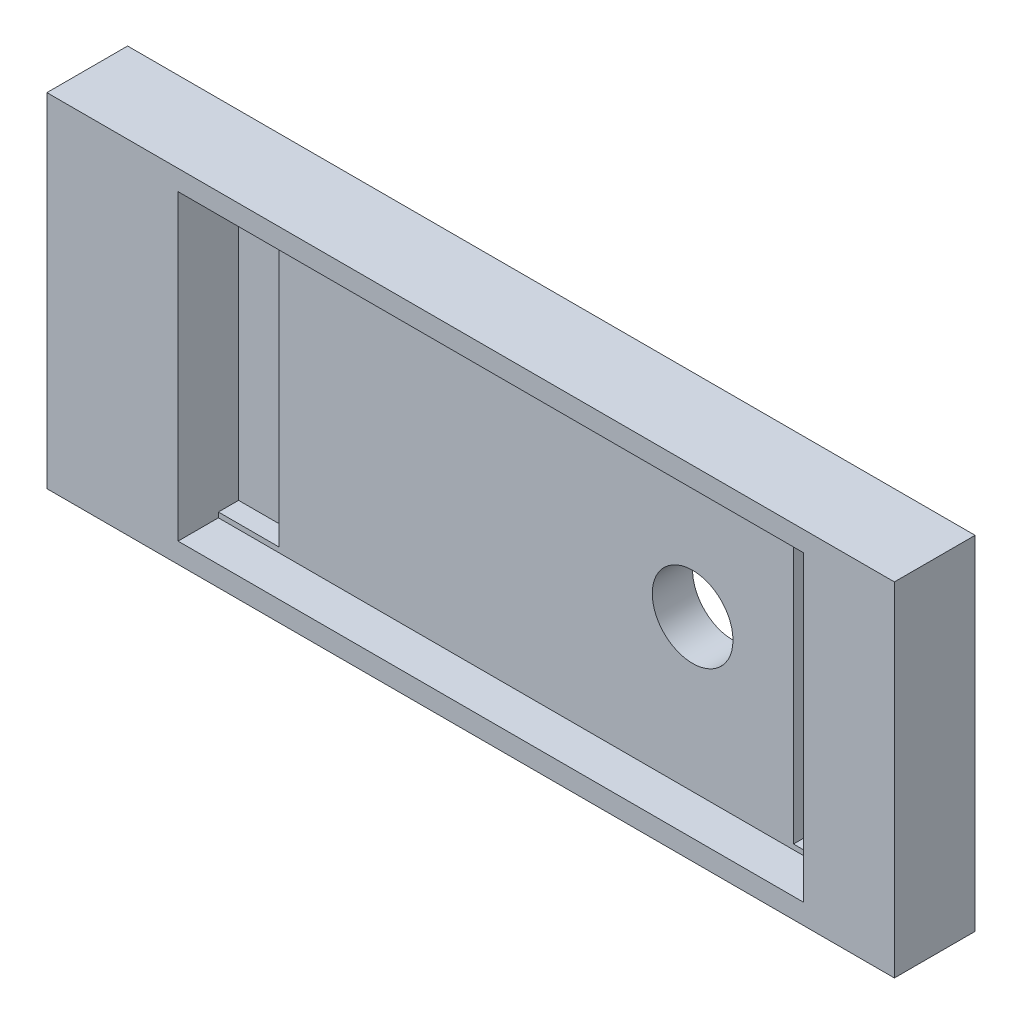
SolidWorks part; units mm, degrees
ref_plane "前视基准面" through (0, 0, 0) normal (0, 0, 1) x (1, 0, 0)
ref_plane "上视基准面" through (0, 0, 0) normal (0, 1, 0) x (1, 0, 0)
ref_plane "右视基准面" through (0, 0, 0) normal (1, 0, 0) x (0, 0, -1)
sketch "草图1" plane through (0, 0, 0) normal (0, 0, 1) x (1, 0, 0)
  line L13 (-30, 8.5) -> (-30, -8.5)
  line L16 (-30, -8.5) -> (12, -8.5)
  line L17 (12, -8.5) -> (12, 0)
  line L20 (12, 0) -> (12, 8.5)
  line L21 (12, 8.5) -> (-30, 8.5)
  circle A1 centre (0, 0) radius 2
  point P3 (11, -8)
  point P9 (11, -37.3394)
  point P10 (-31, 9.618)
  point P11 (-31, -8)
extrude "凸台-拉伸1" add sketch "草图1" along normal blind 2
sketch "草图3" plane through (0, 0, 2) normal (0, 0, 1) x (1, 0, 0)
  line L0 (-20.5, 7.25) -> (-23.5, 7.25)
  line L1 (7.5, 0) -> (7.5, 7.25)
  line L5 (7.5, -7.25) -> (7.5, 0)
  line L6 (7.5, 7.25) -> (5, 7.25)
  line L7 (7.5, 7.25) -> (7.5, -7.25)
  line L8 (7.5, -7.25) -> (5, -7.25)
  line L9 (5, 7.25) -> (5, -7.25)
  line L10 (-23.5, 7.25) -> (-20.5, 7.25)
  line L12 (-23.5, -7.25) -> (-20.5, -7.25)
  line L13 (-20.5, 7.25) -> (-20.5, -7.25)
  line L14 (-23.5, 7.25) -> (-23.5, -7.25)
extrude "切除-拉伸1" cut sketch "草图3" against normal blind 1 contours L13 L10 L12 | L6 L9 L8 L5 L1 region at (-22, 0, 2) region at (6.25, 0, 2)
sketch "草图4" plane through (0, 0, 2) normal (0, 0, 1) x (1, 0, 0)
  line L0 (11, 7.5) -> (-29, 7.5)
  line L1 (-29, 7.5) -> (-29, -7.5)
  line L2 (-29, -7.5) -> (11, -7.5)
  line L3 (11, -7.5) -> (11, 7.5)
  line L4 (12, -8.5) -> (12, 8.5)
  line L5 (12, 8.5) -> (-30, 8.5)
  line L6 (-30, 8.5) -> (-30, -8.5)
  line L7 (-30, -8.5) -> (12, -8.5)
  line L8 (12, -8.5) -> (12, 8.5)
  line L9 (12, 8.5) -> (-30, 8.5)
  line L10 (-30, 8.5) -> (-30, -8.5)
  line L11 (-30, -8.5) -> (12, -8.5)
  dimension "D1" = 0
  dimension "D2" = 1
extrude "凸台-拉伸2" add sketch "草图4" along normal blind 1
sketch "草图6" plane through (0, 0, 2) normal (0, 0, 1) x (1, 0, 0)
  line L0 (11, 7.5) -> (-29, 7.5) construction
  line L1 (-29, -7.5) -> (-23.5, -7.5)
  line L2 (-29, -7.5) -> (-29, 7.5)
  line L3 (-29, 7.5) -> (-23.5, 7.5)
  line L4 (-23.5, -7.5) -> (-23.5, 7.5)
  line L5 (-29, -7.5) -> (11, -7.5) construction
  line L6 (11, 7.5) -> (7.5, 7.5)
  line L7 (11, 7.5) -> (11, -7.5)
  line L8 (11, -7.5) -> (7.5, -7.5)
  line L9 (7.5, 7.5) -> (7.5, -7.5)
extrude "凸台-拉伸4" add sketch "草图6" along normal blind 1
sketch "草图7" plane through (0, 0, 3) normal (0, 0, 1) x (1, 0, 0)
  line L0 (7.5, 7.5) -> (7.5, -7.5)
  line L1 (-23.5, 7.5) -> (7.5, 7.5)
  line L2 (-23.5, 7.5) -> (-23.5, -7.5)
  line L3 (-23.5, -7.5) -> (7.5, -7.5)
  line L4 (-30, -8.5) -> (12, -8.5)
  line L5 (12, -8.5) -> (12, 8.5)
  line L6 (12, 8.5) -> (-30, 8.5)
  line L7 (-30, 8.5) -> (-30, -8.5)
  line L8 (-30, -8.5) -> (12, -8.5)
  line L9 (12, -8.5) -> (12, 8.5)
  line L10 (12, 8.5) -> (-30, 8.5)
  line L11 (-30, 8.5) -> (-30, -8.5)
  dimension "D1" = 0
extrude "凸台-拉伸5" add sketch "草图7" along normal blind 1
